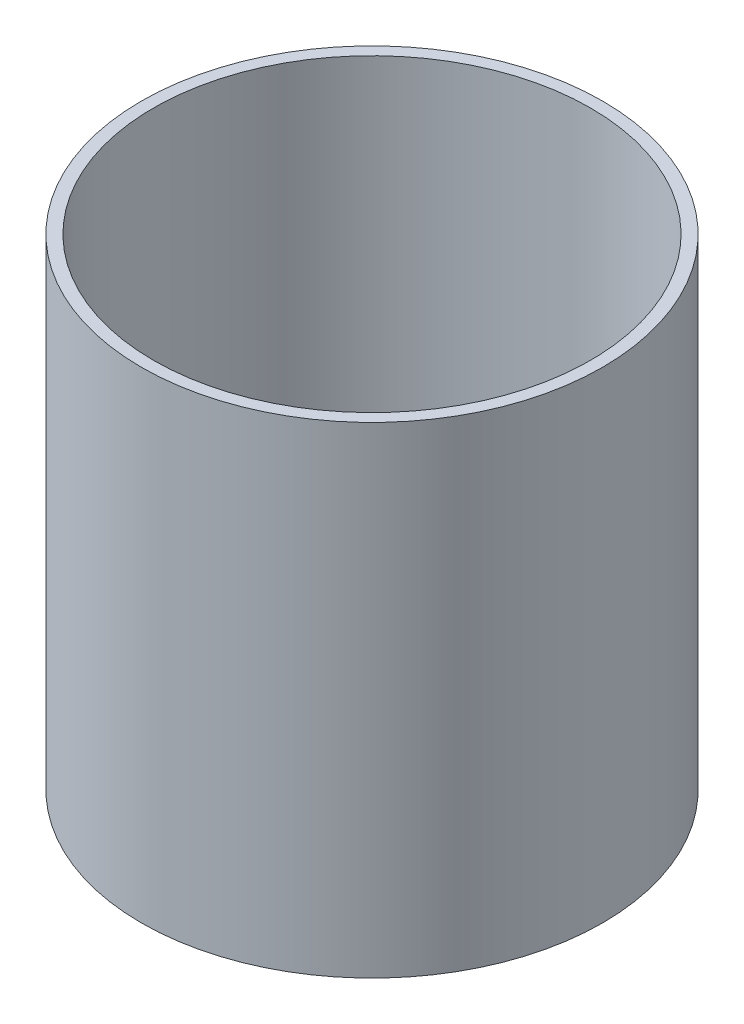
SolidWorks part; units mm, degrees
ref_plane "Front Plane" through (0, 0, 0) normal (0, 0, 1) x (1, 0, 0)
ref_plane "Top Plane" through (0, 0, 0) normal (0, 1, 0) x (1, 0, 0)
ref_plane "Right Plane" through (0, 0, 0) normal (1, 0, 0) x (0, 0, -1)
sketch "Sketch1" plane through (0, 0, 0) normal (0, 1, 0) x (1, 0, 0)
  circle A0 centre (0, 0) radius 54.5
  circle A1 centre (0, 0) radius 57.5
  dimension "D1" = 109
  dimension "D2" = 3
extrude "Boss-Extrude1" add sketch "Sketch1" along normal blind 120
sketch "Sketch2" plane through (-168.9329, 99.4365, -468.1144) normal (0, 0, 1) x (1, 0, 0)
  line L0 (111.4329, 20.5635) -> (111.4329, -99.4365) construction
  line L1 (111.4329, 150.5635) -> (226.4329, 150.5635) construction
  line L2 (111.4329, 150.5635) -> (111.4329, 50.5635) construction
  line L3 (111.4329, 50.5635) -> (226.4329, 50.5635) construction
  line L4 (226.4329, 150.5635) -> (226.4329, 50.5635) construction
  line L5 (226.4329, -99.4365) -> (226.4329, 20.5635) construction
  line L6 (118.4329, 143.5635) -> (118.4329, 57.5635)
  line L7 (118.4329, 57.5635) -> (219.4329, 57.5635)
  line L8 (219.4329, 143.5635) -> (219.4329, 57.5635)
  line L9 (118.4329, 143.5635) -> (219.4329, 143.5635)
  line L10 (111.4329, -99.4365) -> (226.4329, -99.4365) construction
  dimension "D2" = 250
  dimension "D3" = 100
  dimension "D1" = 7
